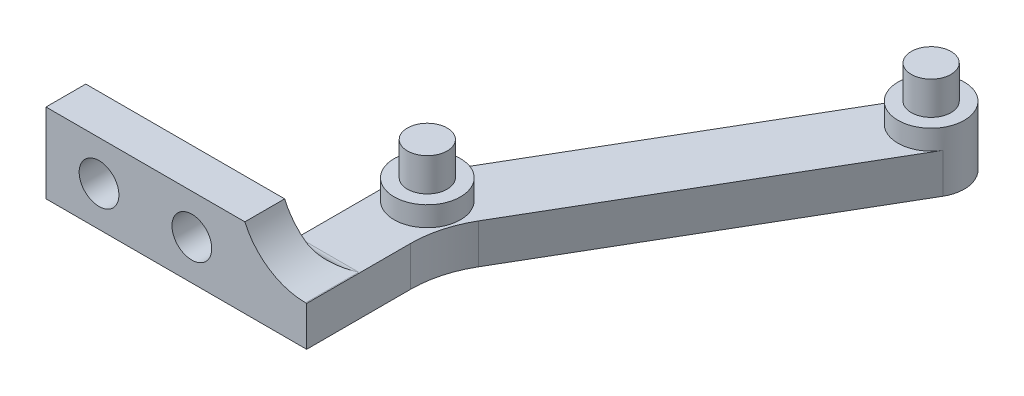
SolidWorks part; units mm, degrees
ref_plane "Front Plane" through (0, 0, 0) normal (0, 0, 1) x (1, 0, 0)
ref_plane "Top Plane" through (0, 0, 0) normal (0, 1, 0) x (1, 0, 0)
ref_plane "Right Plane" through (0, 0, 0) normal (1, 0, 0) x (0, 0, -1)
sketch "Sketch1" plane through (0, 0, 0) normal (0, 1, 0) x (1, 0, 0)
  line L0 (-2.1594, 1.2597) -> (11.8406, 25.2597)
  line L1 (-3, -3) -> (17, -3)
  line L2 (-3, -3) -> (-3, 27)
  line L3 (-3, 27) -> (17, 27)
  line L4 (17, -3) -> (17, 27)
  line L5 (2.1594, -1.2597) -> (16.1594, 22.7403)
  line L6 (2.1594, -1.2597) -> (2.1594, -11.2597)
  line L7 (-2.5, 0) -> (-2.5, -11.2597)
  line L8 (-2.5, -11.2597) -> (2.1594, -11.2597)
  circle A0 centre (0, 0) radius 1.5
  circle A1 centre (14, 24) radius 1.5
  circle A2 centre (0, 0) radius 2.5
  circle A3 centre (14, 24) radius 2.5
  dimension "D1" = 3
  dimension "D4" = 3
  dimension "D6" = 3
  dimension "D5" = 3
  dimension "D7" = 3
  dimension "D2" = 20
  dimension "D3" = 30
  dimension "D8" = 3
  dimension "D10" = 10
  dimension "D9" = 1
extrude "Boss-Extrude1" add sketch "Sketch1" along normal blind 3 contours A3 L0 A2 L5 | L7 L8 L6 L1 | A2 L7 L1 L6 region at (7, 0, -12) region at (-0.6669, 0, 2.4669) region at (-0.1703, 0, 7.1298)
extrude "Boss-Extrude2" add sketch "Sketch1<4>" along normal blind 4.5 contours A2 A0 | A3 A1 region at (0.634, 0, -2.3451) region at (14.634, 0, -26.3451)
sketch "Sketch1<4>" plane through (0, 0, 0) normal (0, 1, 0) x (1, 0, 0) same geometry as "Sketch1"
extrude "Boss-Extrude3" add sketch "Sketch1<5>" along normal blind 7 contours A0 | A1 region at (0, 0, 0) region at (14, 0, -24)
sketch "Sketch1<5>" plane through (0, 0, 0) normal (0, 1, 0) x (1, 0, 0) same geometry as "Sketch1"
sketch "Sketch3" plane through (-2.5, 0, 0) normal (-1, 0, 0) x (0, 0, 1)
  line L1 (11.2597, 0) -> (8.2597, 0)
  line L2 (11.2597, 0) -> (11.2597, 6)
  line L3 (11.2597, 6) -> (8.2597, 6)
  line L4 (8.2597, 0) -> (8.2597, 6)
  dimension "D1" = 3
  dimension "D2" = 6
extrude "Boss-Extrude4" add sketch "Sketch3" along normal blind 15
sketch "Sketch4" plane through (0, 0, 8.2597) normal (0, 0, -1) x (-1, 0, 0)
  line L0 (17.5, 3) -> (0.4563, 3) construction
  line L1 (17.5, 6) -> (17.5, 0) construction
  line L2 (2.5, 6) -> (2.5, 3) construction
  circle A0 centre (6.5, 3) radius 1.5
  circle A1 centre (13.5, 3) radius 1.5
  dimension "D1" = 3
  dimension "D2" = 3
  dimension "D3" = 4
  dimension "D4" = 4
extrude "Cut-Extrude1" cut sketch "Sketch4" against normal blind 20
fillet "Fillet1" radius 5 1 edges at (-2.5, 3, 9.7597)
fillet "Fillet2" radius 1 2 edges at (-0.2087, 3, 8.2597) (-2.5, 1.5, 8.2597)
fillet "Fillet3" radius 8 1 edges at (2.1594, 1.5, 1.2597)
